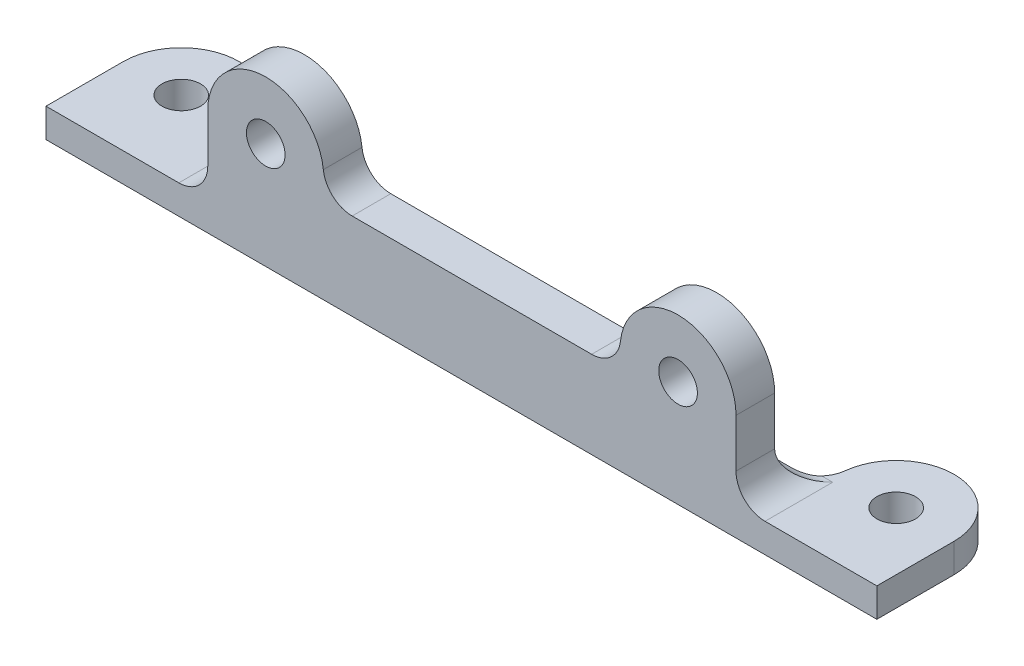
SolidWorks part; units mm, degrees
ref_plane "Front Plane" through (0, 0, 0) normal (0, 0, 1) x (1, 0, 0)
ref_plane "Top Plane" through (0, 0, 0) normal (0, 1, 0) x (1, 0, 0)
ref_plane "Right Plane" through (0, 0, 0) normal (1, 0, 0) x (0, 0, -1)
sketch "Sketch1" plane through (0, 0, 0) normal (0, 1, 0) x (1, 0, 0)
  line L0 (0, 0) -> (74, 0) construction
  line L1 (74, -2) -> (0, -2)
  line L2 (-6, 0) -> (80, 0)
  line L3 (-6, 0) -> (-6, -8)
  line L4 (-6, -8) -> (80, -8)
  line L5 (80, 0) -> (80, -8)
  circle A0 centre (0, 0) radius 2
  circle A1 centre (74, 0) radius 2
  circle A2 centre (0, 0) radius 6
  circle A3 centre (74, 0) radius 6
  dimension "D1" = 4
  dimension "D2" = 4
  dimension "D4" = 4
  dimension "D5" = 4
  dimension "D3" = 74
  dimension "D6" = 8
extrude "Boss-Extrude1" add sketch "Sketch1" along normal blind 3 contours A3 L1 A2 L3 L4 L5 | L2 A2 L1 A0 | L2 A2 A0 | L1 A2 L2 A0 | L2 A3 A1 | L2 A3 L1 A1 | L1 A3 L2 A1
sketch "Sketch2" plane through (0, 0, 8) normal (0, 0, 1) x (1, 0, 0)
  line L0 (37, 3) -> (37, 11) construction
  line L1 (-6, 3) -> (80, 3) construction
  line L2 (10.746, 11) -> (10.746, 3)
  line L3 (65.4242, 11) -> (65.4242, 3)
  line L4 (16.746, 9) -> (59.4242, 9)
  circle A0 centre (16.746, 11) radius 2
  circle A1 centre (59.4242, 11) radius 2
  circle A2 centre (16.746, 11) radius 6
  circle A3 centre (59.4242, 11) radius 6
  dimension "D1" = 4
  dimension "D2" = 4
  dimension "D3" = 4
  dimension "D4" = 4
  dimension "D5" = 8
extrude "Boss-Extrude2" add sketch "Sketch2" against normal blind 4
fillet "Fillet1" radius 3 5 edges at (22.4028, 9, 6) (53.7674, 9, 6) (65.4242, 3, 6) (10.746, 3, 6) (38.0851, 3, 4)
fillet "Fillet2" radius 3 1 edges at (68.3431, 1.5005, 2)
fillet "Fillet3" radius 3 1 edges at (5.6569, 1.5, 2)
